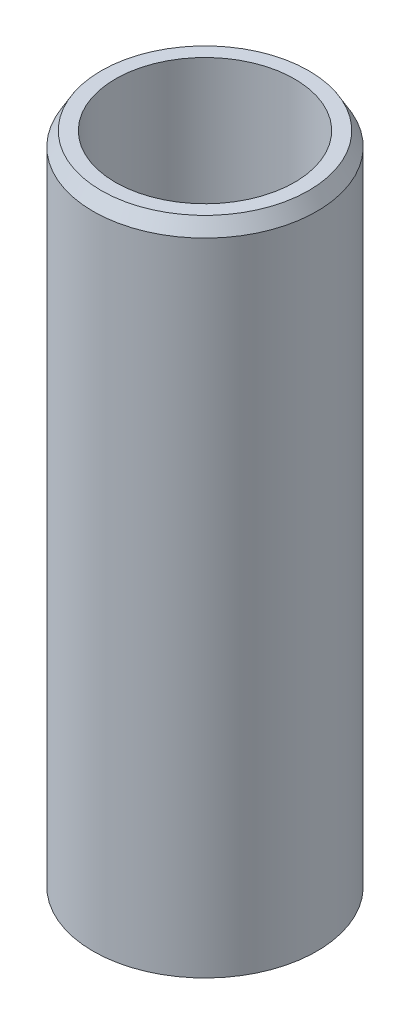
SolidWorks part; units mm, degrees
ref_plane "Front Plane" through (0, 0, 0) normal (0, 0, 1) x (1, 0, 0)
ref_plane "Top Plane" through (0, 0, 0) normal (0, 1, 0) x (1, 0, 0)
ref_plane "Right Plane" through (0, 0, 0) normal (1, 0, 0) x (0, 0, -1)
sketch "Sketch1" plane through (0, 0, 0) normal (0, 1, 0) x (1, 0, 0)
  circle A0 centre (0, 0) radius 45
  dimension "SHAFT_OD" = 90
extrude "Boss-Extrude1" add sketch "Sketch1" along normal blind 266.6039
sketch "Sketch2" plane through (0, 0, 0) normal (0, 1, 0) x (1, 0, 0)
  circle A0 centre (0, 0) radius 36.0391
  dimension "BORE_D" = 72.0782
extrude "Cut-Extrude1" cut sketch "Sketch2" along normal through all
chamfer "Chamfer1" distance 5.6299 angle 30 2 edges at (0, 266.6039, 45) (0, 0, 45) first distance on face at (0, 266.6039, 45) first distance on face at (0, 0, 36.0391)
